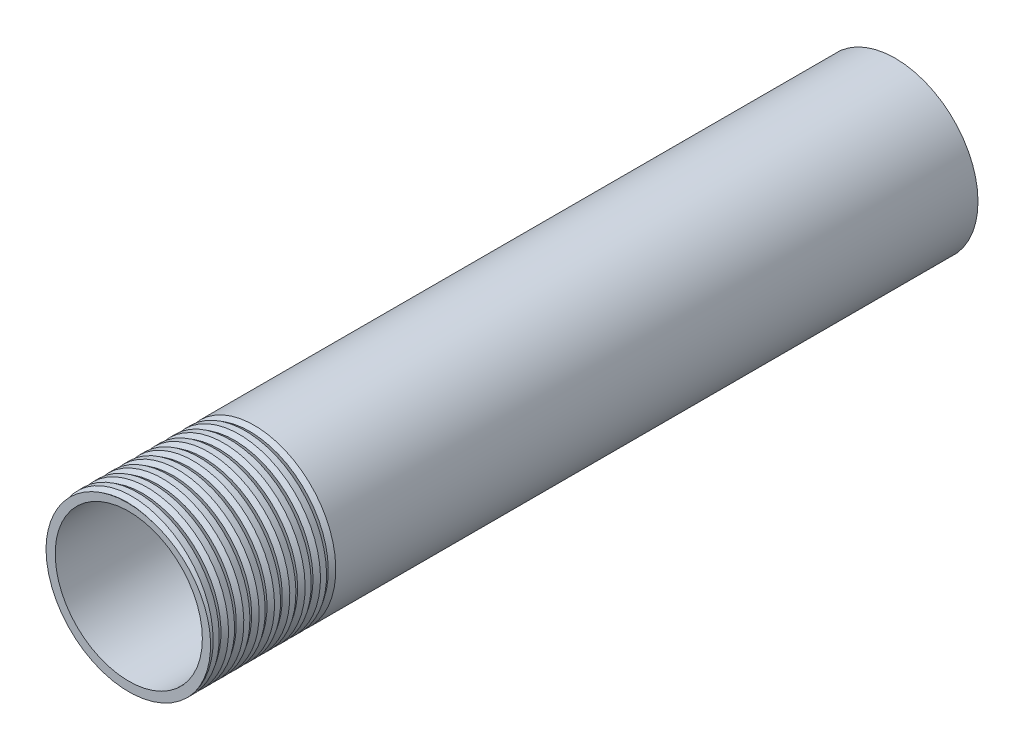
SolidWorks part; units mm, degrees
ref_plane "Front Plane" through (0, 0, 0) normal (0, 0, 1) x (1, 0, 0)
ref_plane "Top Plane" through (0, 0, 0) normal (0, 1, 0) x (1, 0, 0)
ref_plane "Right Plane" through (0, 0, 0) normal (1, 0, 0) x (0, 0, -1)
sketch "Sketch1" plane through (0, 0, 0) normal (0, 0, 1) x (1, 0, 0)
  circle A0 centre (0, 0) radius 13.5
  circle A1 centre (0, 0) radius 12
  dimension "D1" = 1.5
  dimension "D2" = 27
extrude "Boss-Extrude1" add sketch "Sketch1" along normal blind 125
sketch "Sketch3" plane through (0, 0, 125) normal (0, 0, 1) x (1, 0, 0)
  circle A2 centre (0, 0) radius 13.5 construction
  circle A3 centre (0, 0) radius 13.5
curve "Helix/Spiral2" pitch 2.5 height 20 radius 13.5 left hand yes centre (0, 0, 125) axis (0, 0, -1) start towards (-1, 0, 0)
sketch "Sketch6" plane through (0, 0, 0) normal (0, 1, 0) x (1, 0, 0)
  line L3 (-13.5, -125) -> (-13.5, -123.4929)
  line L4 (-13.5, 0) -> (-13.5, -125) construction
  line L5 (-13.5, -123.4929) -> (-13.0298, -124.2465)
  line L6 (-13.5, -125) -> (-13.0298, -124.2465)
sweep "Cut-Sweep5" cut profiles "Sketch6" path "Helix/Spiral2" align with end faces yes
